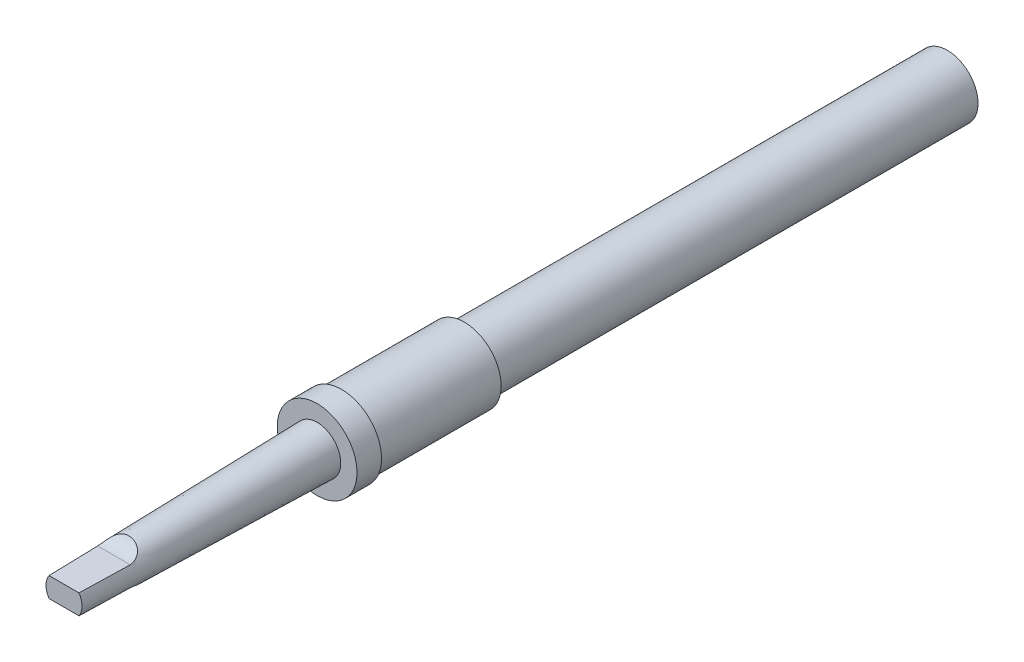
SolidWorks part; units mm, degrees
ref_plane "Front Plane" through (0, 0, 0) normal (0, 0, 1) x (1, 0, 0)
ref_plane "Top Plane" through (0, 0, 0) normal (0, 1, 0) x (1, 0, 0)
ref_plane "Right Plane" through (0, 0, 0) normal (1, 0, 0) x (0, 0, -1)
sketch "Sketch3" plane through (0, 0, 0) normal (1, 0, 0) x (0, 0, -1)
  line L0 (0, 0) -> (-259.5858, 0) construction
  line L4 (-228.6, 0) -> (0, 0)
  line L6 (-228.6, 4.6617) -> (-163.1, 6.1099)
  line L7 (-163.1, 6.1099) -> (-163.1, 10.3187)
  line L8 (-163.1, 10.3187) -> (-156.75, 10.3187)
  line L9 (-156.75, 10.3187) -> (-156.75, 9.525)
  line L10 (-156.75, 9.525) -> (-125, 9.525)
  line L11 (-125, 9.525) -> (-125, 7.9375)
  line L12 (-125, 7.9375) -> (0, 7.9375)
  line L13 (0, 7.9375) -> (0, 0)
  line L15 (-166.6, 6.0325) -> (-166.6, 0) construction
  line L16 (-163.1, 6.1099) -> (-219.4233, 6.1099) construction
  line L22 (-228.6, 4.6617) -> (-228.6, 0)
  point P3 (-166.6, 6.0325)
  dimension "D2" = 65.5
  dimension "D3" = 20.6375
  dimension "D4" = 19.05
  dimension "D5" = 15.875
  dimension "D6" = 228.6
  dimension "D7" = 31.75
  dimension "D8" = 6.35
  dimension "D10" = 3.5
  dimension "D11" = 12.065
  dimension "D13" = 1.267
revolve "Revolve2" add sketch "Sketch3" angle 360 about L0 region at (0, 3.895, 107.2252)
sketch "Sketch4" plane through (0, 0, 0) normal (1, 0, 0) x (0, 0, -1)
  line L0 (-228.6, 2.5781) -> (-228.6, -2.5781) construction
  line L1 (-261.7454, 6.5773) -> (-216.7439, 6.5773)
  line L2 (-261.7454, 6.5773) -> (-261.7454, 2.5781)
  line L3 (-261.7454, 2.5781) -> (-215.6573, 2.5781)
  line L5 (-261.7324, -2.5781) -> (-215.6573, -2.5781)
  line L6 (-261.7324, -2.5781) -> (-261.7324, -6.5773)
  line L7 (-261.7324, -6.5773) -> (-216.7439, -6.5773)
  line L10 (-228.6, 4.6617) -> (-228.6, -4.6617) construction
  line L12 (-228.6, -4.6617) -> (-163.1, -6.1099) construction
  line L13 (-211.8187, -5.0327) -> (-216.7439, -6.5773)
  line L14 (11.3506, 0) -> (-11.3506, 0) construction
  line L15 (-211.8187, 5.0327) -> (-216.7439, 6.5773)
  arc A0 (-215.6573, -2.5781) -> (-211.8187, -5.0327) centre (-216.1358, -7.5552) cw
  arc A1 (-215.6573, 2.5781) -> (-211.8187, 5.0327) centre (-216.1358, 7.5552) ccw
  point P3 (-216.7569, 6.577)
  point P23 (-215.6573, 8.1429)
  point P24 (-228.6, 0)
  dimension "D2" = 5
  dimension "D3" = 5
  dimension "D1" = 5.1562
extrude "Cut-Extrude1" cut sketch "Sketch4" against normal through all both and the other way through all contours L1 L2 L3 | L5 L6 L7 region at (0, 4.5689, 237.618) region at (0, -4.5689, 237.6115)
